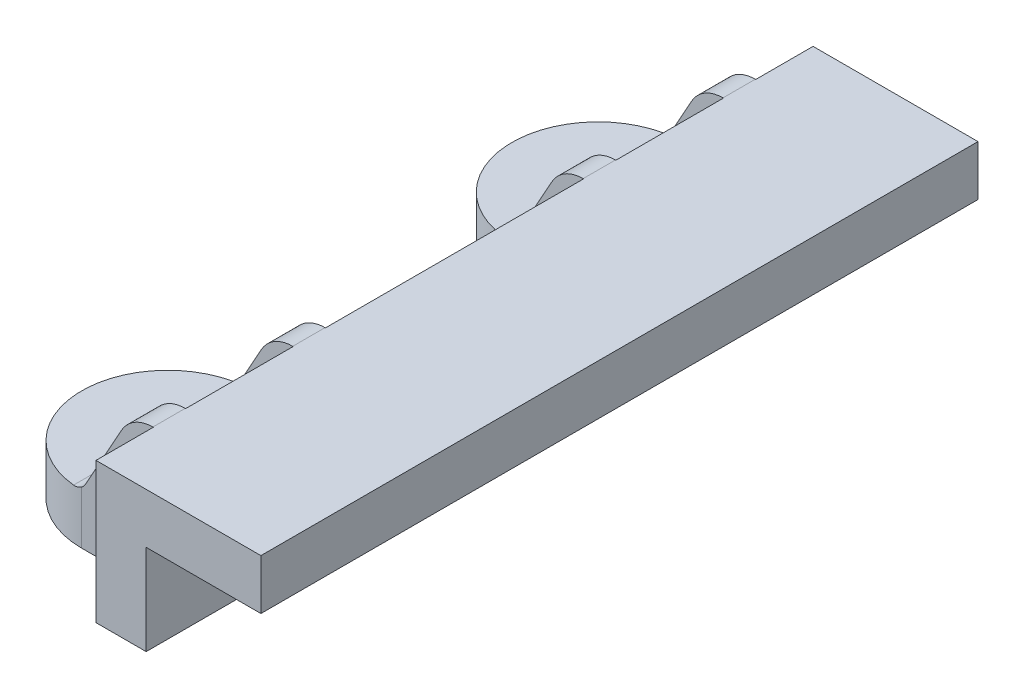
SolidWorks part; units mm, degrees
material "Acrílico (Impacto medio-alto)"
ref_plane "Alzado" through (0, 0, 0) normal (0, 0, 1) x (1, 0, 0)
ref_plane "Planta" through (0, 0, 0) normal (0, 1, 0) x (1, 0, 0)
ref_plane "Vista lateral" through (0, 0, 0) normal (1, 0, 0) x (0, 0, -1)
sketch "Croquis1" plane through (0, 0, 0) normal (0, 0, 1) x (1, 0, 0)
  line L0 (0, 0) -> (0, 9.8)
  line L1 (0, 9.8) -> (11.5, 9.8)
  line L2 (11.5, 9.8) -> (11.5, 6.3)
  line L3 (11.5, 6.3) -> (3.5, 6.3)
  line L4 (3.5, 6.3) -> (3.5, 0)
  line L5 (3.5, 0) -> (0, 0)
  dimension "D1" = 3.5
  dimension "D2" = 8
  dimension "D3" = 3.5
  dimension "D4" = 6.3
extrude "Saliente-Extruir1" add sketch "Croquis1" along normal mid plane 50
sketch "Croquis2" plane through (0, 0, 0) normal (0, 1, 0) x (1, 0, 0)
  line L0 (0, -25) -> (0, 25) construction
  line L1 (0, 9) -> (-5, 9)
  line L2 (0, 9) -> (0, 21)
  line L3 (0, 21) -> (-5, 21)
  line L6 (11.5, 25) -> (0, 25) construction
  arc A0 (-5, 21) -> (-5, 9) centre (-5, 15) ccw
  circle A2 centre (-4.75, 15) radius 2.25
  point P8 (0, 0)
  dimension "D4" = 4.5
  dimension "D1" = 10
  dimension "D2" = 12
  dimension "D3" = 5
  dimension "D5" = 4.75
extrude "Saliente-Extruir2" add sketch "Croquis2" along normal blind 3.5
sketch "Croquis3" plane through (0, 0, -9) normal (0, 0, 1) x (1, 0, 0)
  line L1 (0, 9.8) -> (0, 3.5)
  line L2 (0, 9.8) -> (0, 0) construction
  line L3 (-5, 3.5) -> (0, 3.5) construction
  line L4 (0, 3.5) -> (-5, 3.5)
  line L5 (-5, 3.5) -> (-1.5, 9.8)
  line L6 (-1.5, 9.8) -> (0, 9.8)
  dimension "D1" = 1.5
extrude "Saliente-Extruir3" add sketch "Croquis3" against normal blind 2.25
fillet "Redondeo3" radius 1 1 edges at (-5, 3.5, -10.125)
fillet "Redondeo5" radius 2.5 1 edges at (-1.5, 9.8, -10.125)
ref_plane "Plano1" through (0, 0, -15) normal (0, 0, -1) x (-1, 0, 0)
mirror "Simetría1" about plane through (0, 0, -15) normal (0, 0, -1) of "Saliente-Extruir3", "Redondeo3", "Redondeo5"
mirror "Simetría4" about plane through (0, 0, 0) normal (0, 0, 1) of "Saliente-Extruir2", "Saliente-Extruir3", "Redondeo3", "Redondeo5"
ref_plane "Plano2" through (0, 0, 15) normal (0, 0, -1) x (-1, 0, 0)
sketch "Croquis4" plane through (0, 0, 21) normal (0, 0, 1) x (1, 0, 0)
  line L0 (0, 3.5) -> (-5, 3.5)
  line L1 (-5, 3.5) -> (-1.5, 9.8)
  line L2 (0, 9.8) -> (-1.5, 9.8)
  line L4 (0, 3.5) -> (0, 9.8)
  dimension "D1" = 1.5
extrude "Saliente-Extruir4" add sketch "Croquis4" against normal blind 2.25
fillet "Redondeo6" radius 2.5 1 edges at (-1.5, 9.8, 19.875)
fillet "Redondeo7" radius 1 1 edges at (-5, 3.5, 19.875)
